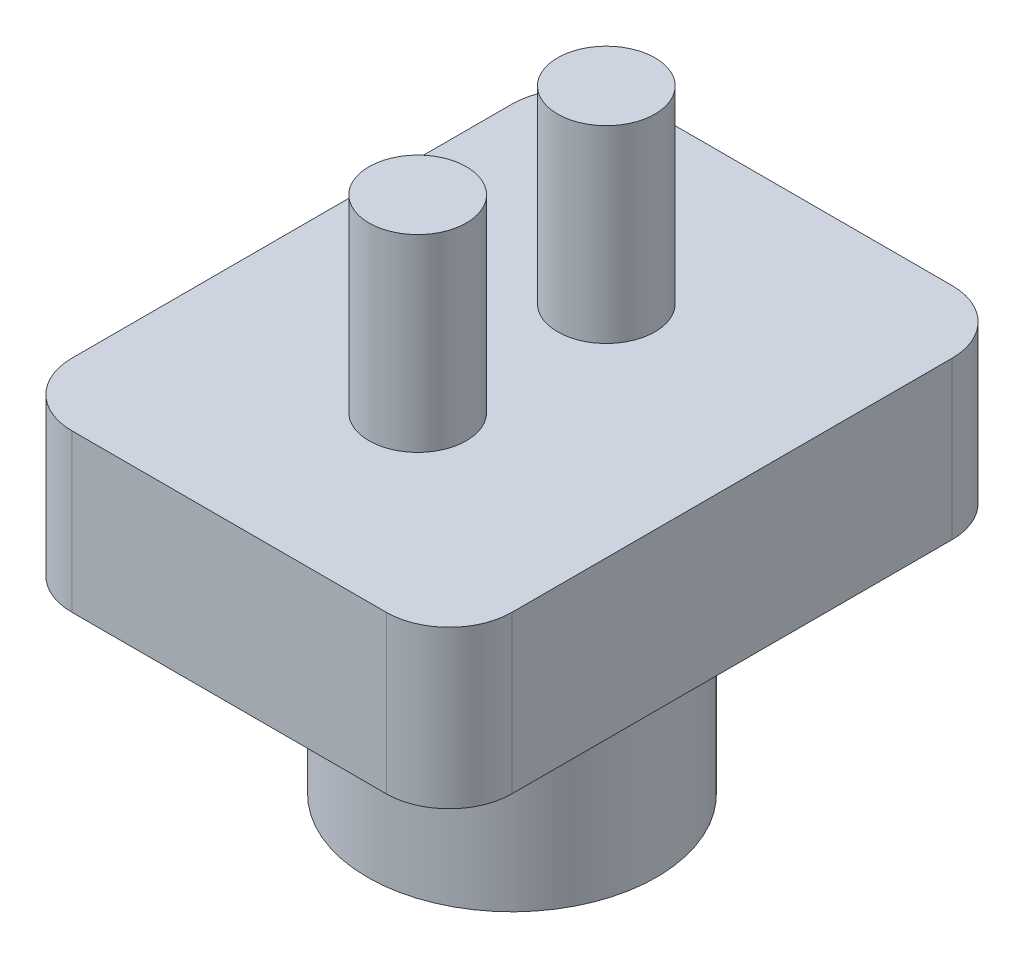
SolidWorks part; units mm, degrees
ref_plane "Alzado" through (0, 0, 0) normal (0, 0, 1) x (1, 0, 0)
ref_plane "Planta" through (0, 0, 0) normal (0, 1, 0) x (1, 0, 0)
ref_plane "Vista lateral" through (0, 0, 0) normal (1, 0, 0) x (0, 0, -1)
sketch "Sketch1" plane through (0, 0, 0) normal (0, 1, 0) x (1, 0, 0)
  line L1 (-7, -9) -> (7, -9)
  line L2 (-7, -9) -> (-7, 9)
  line L3 (-7, 9) -> (7, 9)
  line L4 (7, -9) -> (7, 9)
  line L5 (-7, -9) -> (7, 9) construction
  line L6 (-7, 9) -> (7, -9) construction
  circle A0 centre (0, 0) radius 2.8
  circle A1 centre (0, 0) radius 4.6
  point P7 (0, 0)
  dimension "D1" = 5.6
  dimension "D2" = 9.2
  dimension "D3" = 18
  dimension "D4" = 14
extrude "Acople palito" add sketch "Sketch1" along normal blind 7 contours A1 A0 region at (-4.4699, 0, 0)
extrude "Cuerpo" add sketch "Sketch1<3>" along normal blind 5 from offset 7 contours L1 L4 L3 L2 A1 | A1 A0 | A0 region at (-6.772, 0, 0) region at (0, 0, 0) region at (-4.4699, 0, 0)
sketch "Sketch1<3>" plane through (0, 0, 0) normal (0, 1, 0) x (1, 0, 0) same geometry as "Sketch1"
sketch "Sketch2" plane through (0, 12, 0) normal (0, 1, 0) x (1, 0, 0)
  line L0 (0, -3) -> (0, 3) construction
  circle A0 centre (0, 3) radius 1.55
  circle A1 centre (0, -3) radius 1.55
  point P4 (0, 0)
  dimension "D1" = 3.1
  dimension "D2" = 3.1
  dimension "D3" = 3
  dimension "D4" = 6
extrude "Acople sensor" add sketch "Sketch2" along normal blind 6
fillet "Fillet1" radius 2 4 edges at (7, 9.5, 9) (-7, 9.5, 9) (-7, 9.5, -9) (7, 9.5, -9)
